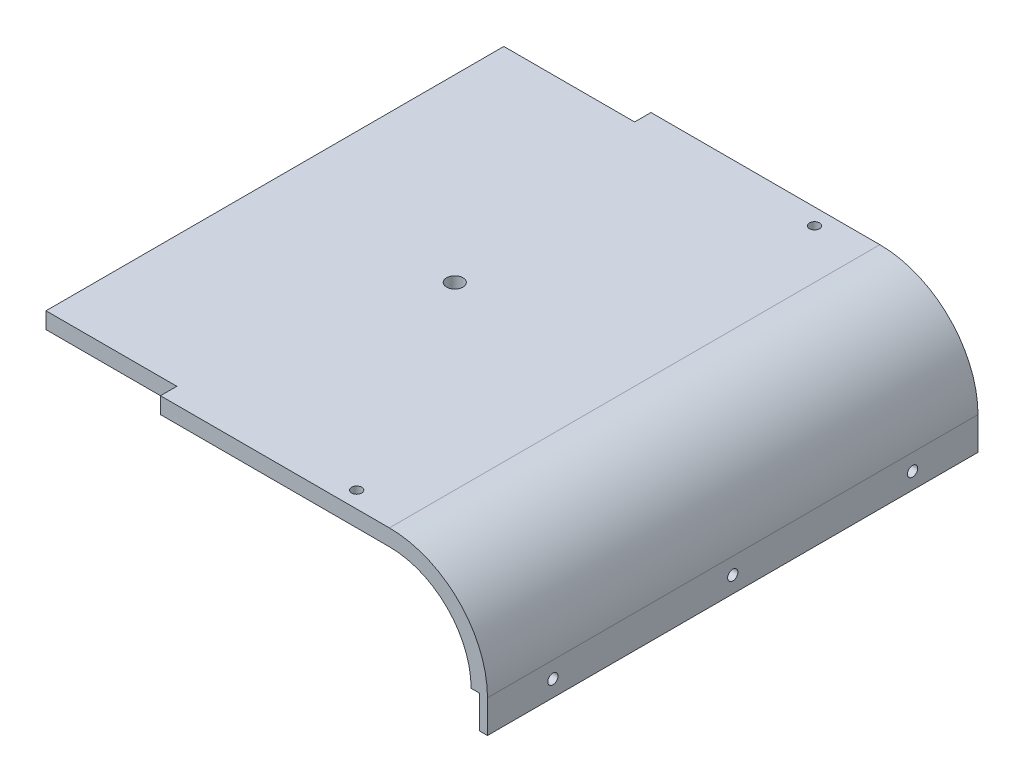
SolidWorks part; units mm, degrees
ref_plane "Front Plane" through (0, 0, 0) normal (0, 0, 1) x (1, 0, 0)
ref_plane "Top Plane" through (0, 0, 0) normal (0, 1, 0) x (1, 0, 0)
ref_plane "Right Plane" through (0, 0, 0) normal (1, 0, 0) x (0, 0, -1)
sketch "Sketch1" plane through (0, 0, 0) normal (0, 0, 1) x (1, 0, 0)
  line L0 (-139.7, 0) -> (139.7, 0)
  line L1 (139.7, 0) -> (139.7, -152.4) construction
  line L2 (139.7, -76.2) -> (215.9, -76.2) construction
  line L3 (-139.7, -12.7) -> (139.7, -12.7)
  line L4 (-139.7, 0) -> (-139.7, -12.7)
  line L5 (215.9, -76.2) -> (203.2, -76.2)
  circle A0 centre (139.7, -76.2) radius 76.2 construction
  arc A1 (139.7, 0) -> (215.9, -76.2) centre (139.7, -76.2) cw
  arc A2 (139.7, -12.7) -> (203.2, -76.2) centre (139.7, -76.2) cw
  point P4 (0, 0)
  dimension "D1" = 152.4
  dimension "D2" = 355.6
  dimension "D3" = 12.7
extrude "Boss-Extrude1" add sketch "Sketch1" along normal blind 190.5 and the other way blind 190.5
sketch "Sketch2" plane through (0, -76.2, 0) normal (0, -1, 0) x (1, 0, 0)
  line L0 (203.2, 190.5) -> (215.9, 190.5) construction
  line L1 (209.55, 190.5) -> (215.9, 190.5)
  line L2 (209.55, 190.5) -> (209.55, -190.5)
  line L3 (209.55, -190.5) -> (215.9, -190.5)
  line L4 (215.9, 190.5) -> (215.9, -190.5)
extrude "Boss-Extrude2" add sketch "Sketch2" along normal blind 25.4
sketch "Sketch3" plane through (215.9, 0, 0) normal (1, 0, 0) x (0, 0, -1)
  line L0 (-190.5, -88.9) -> (190.5, -88.9) construction
  line L1 (-190.5, -101.6) -> (-190.5, -76.2) construction
  line L2 (190.5, -101.6) -> (190.5, -76.2) construction
  line L3 (0, -76.2) -> (0, -101.6) construction
  line L4 (190.5, -76.2) -> (-190.5, -76.2) construction
  line L5 (190.5, -101.6) -> (-190.5, -101.6) construction
  line L6 (139.7, -76.2) -> (139.7, -101.6) construction
  line L7 (-139.7, -76.2) -> (-139.7, -101.6) construction
  circle A0 centre (-139.7, -88.9) radius 3.9687
  circle A1 centre (0, -88.9) radius 3.9687
  circle A2 centre (139.7, -88.9) radius 3.9687
  dimension "D3" = 7.9375
  dimension "D1" = 139.7
  dimension "D2" = 139.7
extrude "Cut-Extrude1" cut sketch "Sketch3" against normal blind 25.4
sketch "Sketch4" plane through (0, 0, 0) normal (0, 1, 0) x (1, 0, 0)
  circle A0 centre (0, 0) radius 6.35
  dimension "D1" = 12.7
extrude "Cut-Extrude2" cut sketch "Sketch4" against normal blind 17.78
sketch "Sketch5" plane through (0, 0, 0) normal (0, 1, 0) x (1, 0, 0)
  line L0 (139.7, 0) -> (101.6, 0) construction
  line L1 (139.7, 190.5) -> (139.7, -190.5) construction
  line L2 (-139.7, 190.5) -> (-139.7, -190.5) construction
  line L3 (0, 177.8) -> (0, -177.8) construction
  line L4 (101.6, 177.8) -> (101.6, -177.8) construction
  line L5 (-101.6, -177.8) -> (-101.6, 177.8) construction
  line L6 (139.7, -190.5) -> (-139.7, -190.5) construction
  line L7 (-101.6, 0) -> (-139.7, 0) construction
  line L8 (-101.6, 0) -> (0, 0) construction
  line L9 (0, 0) -> (101.6, 0) construction
  line L12 (-101.6, -177.8) -> (-139.7, -177.8)
  line L13 (-139.7, -177.8) -> (-139.7, -190.5)
  line L14 (-139.7, -190.5) -> (-38.1, -190.5)
  line L15 (-38.1, -190.5) -> (-38.1, -177.8)
  line L16 (-38.1, -177.8) -> (-101.6, -177.8)
  line L27 (-38.1, 190.5) -> (-38.1, 177.8)
  line L28 (-139.7, 190.5) -> (-38.1, 190.5)
  line L29 (-139.7, 177.8) -> (-139.7, 190.5)
  line L30 (-101.6, 177.8) -> (-139.7, 177.8)
  line L31 (-38.1, 177.8) -> (-101.6, 177.8)
  circle A1 centre (101.6, -177.8) radius 3.937
  circle A2 centre (101.6, 177.8) radius 3.937
  point P11 (0, 0)
  point P15 (101.6, 0)
  point P18 (-101.6, 0)
  dimension "D3" = 7.874
  dimension "D1" = 12.7
  dimension "D2" = 203.2
  dimension "D4" = 101.6
extrude "Cut-Extrude3" cut sketch "Sketch5" against normal through all
